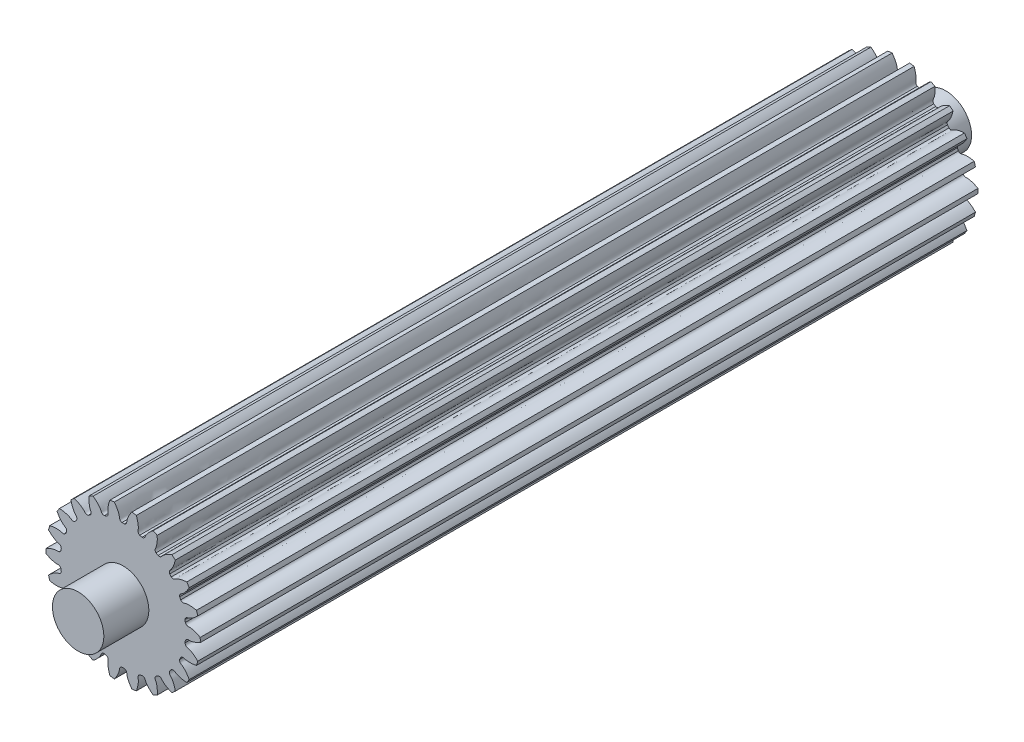
SolidWorks part; units mm, degrees
ref_plane "前视基准面" through (0, 0, 0) normal (0, 0, 1) x (1, 0, 0)
ref_plane "上视基准面" through (0, 0, 0) normal (0, 1, 0) x (1, 0, 0)
ref_plane "右视基准面" through (0, 0, 0) normal (1, 0, 0) x (0, 0, -1)
sketch "草图1" plane through (0, 0, 0) normal (0, 0, 1) x (1, 0, 0)
  circle A0 centre (0, 0) radius 12
extrude "凸台-拉伸1" add sketch "草图1" along normal blind 30
ref_axis "基准轴1" through (0, 0, -1.5) along (0, 0, 1)
sketch "草图2" plane through (0, 0, 0) normal (0, 0, 1) x (1, 0, 0)
  line L0 (0, 0) -> (0, 12) construction
  circle A0 centre (0, 0) radius 12 construction
  arc A1 (0.1857, 9.7482) -> (-0.1857, 9.7482) centre (0, 0) ccw
  arc A2 (3.0856, 13.5599) -> (-3.0856, 13.5599) centre (0, 0) ccw
  spline S0 degree 3 poles (0.1857, 9.7482) (0.5882, 9.8762) (0.5483, 10.1518) (0.5996, 10.4216) (0.606, 10.4519) (0.6139, 10.4862) (0.6235, 10.5243) (0.6349, 10.5661) (0.6484, 10.6117) (0.664, 10.661) (0.6819, 10.7139) (0.7023, 10.7703) (0.7253, 10.8301) (0.7511, 10.8933) (0.7797, 10.9597) (0.8114, 11.0293) (0.8462, 11.1021) (0.8843, 11.1778) (0.9259, 11.2563) (0.9711, 11.3377) (1.0199, 11.4217) (1.0726, 11.5082) (1.1292, 11.5972) (1.1899, 11.6884) (1.2547, 11.7818) (1.3238, 11.8773) (1.3973, 11.9746) (1.4753, 12.0737) (1.5579, 12.1744) (1.6452, 12.2766) (1.7372, 12.3802) (1.8341, 12.4849) (1.9359, 12.5906) (2.0428, 12.6972) (2.1547, 12.8044) (2.2718, 12.9123) (2.3942, 13.0205) (2.5218, 13.1289) (2.6548, 13.2373) (2.8415, 13.3834) (2.9864, 13.49) (3.0856, 13.5599) knots 0 0 0 0 0.157021 0.162531 0.168888 0.176093 0.184146 0.193046 0.202794 0.213389 0.224833 0.237123 0.250262 0.264248 0.279082 0.294763 0.311292 0.328669 0.346893 0.365965 0.385884 0.406652 0.428266 0.450729 0.474039 0.498197 0.523202 0.549055 0.575756 0.603304 0.6317 0.660944 0.691035 0.721974 0.75376 0.786395 0.819876 0.854206 0.889383 0.925408 1 1 1 1
  spline S1 degree 3 poles (-0.1857, 9.7482) (-0.5882, 9.8762) (-0.5483, 10.1518) (-0.5996, 10.4216) (-0.606, 10.4519) (-0.6139, 10.4862) (-0.6235, 10.5243) (-0.6349, 10.5661) (-0.6484, 10.6117) (-0.664, 10.661) (-0.6819, 10.7139) (-0.7023, 10.7703) (-0.7253, 10.8301) (-0.7511, 10.8933) (-0.7797, 10.9597) (-0.8114, 11.0293) (-0.8462, 11.1021) (-0.8843, 11.1778) (-0.9259, 11.2563) (-0.9711, 11.3377) (-1.0199, 11.4217) (-1.0726, 11.5082) (-1.1292, 11.5972) (-1.1899, 11.6884) (-1.2547, 11.7818) (-1.3238, 11.8773) (-1.3973, 11.9746) (-1.4753, 12.0737) (-1.5579, 12.1744) (-1.6452, 12.2766) (-1.7372, 12.3802) (-1.8341, 12.4849) (-1.9359, 12.5906) (-2.0428, 12.6972) (-2.1547, 12.8044) (-2.2718, 12.9123) (-2.3942, 13.0205) (-2.5218, 13.1289) (-2.6548, 13.2373) (-2.8415, 13.3834) (-2.9864, 13.49) (-3.0856, 13.5599) knots 0 0 0 0 0.157021 0.162531 0.168888 0.176093 0.184146 0.193046 0.202794 0.213389 0.224833 0.237123 0.250262 0.264248 0.279082 0.294763 0.311292 0.328669 0.346893 0.365965 0.385884 0.406652 0.428266 0.450729 0.474039 0.498197 0.523202 0.549055 0.575756 0.603304 0.6317 0.660944 0.691035 0.721974 0.75376 0.786395 0.819876 0.854206 0.889383 0.925408 1 1 1 1
extrude "切除-拉伸1" cut sketch "草图2" along normal through all
pattern_circular "阵列(圆周)1" count 22 every 16.364 about axis through (0, 0, -1.5) along (0, 0, 1) of "切除-拉伸1"
sketch "草图3" plane through (0, 0, 0) normal (0, 0, 1) x (1, 0, 0)
  circle A0 centre (0, 0) radius 11 construction
  dimension "Dn" = 22
sketch "草图4" plane through (0, 0, 0) normal (0, 0, -1) x (-1, 0, 0)
  arc A45 (2.9245, 9.3011) -> (2.5682, 9.4057) centre (0, 0) ccw
  arc A46 (2.0557, 11.8226) -> (1.3584, 11.9229) centre (0, 0) ccw
  arc A47 (0.1857, 9.7482) -> (-0.1857, 9.7482) centre (0, 0) ccw
  arc A48 (-1.3584, 11.9229) -> (-2.0557, 11.8226) centre (0, 0) ccw
  arc A49 (-2.5682, 9.4057) -> (-2.9245, 9.3011) centre (0, 0) ccw
  arc A50 (-4.6624, 11.0572) -> (-5.3032, 10.7646) centre (0, 0) ccw
  arc A51 (-5.1141, 8.3011) -> (-5.4265, 8.1004) centre (0, 0) ccw
  arc A52 (-7.5887, 9.2958) -> (-8.1211, 8.8344) centre (0, 0) ccw
  arc A53 (-7.2456, 6.5241) -> (-7.4888, 6.2434) centre (0, 0) ccw
  arc A54 (-9.9003, 6.7812) -> (-10.2811, 6.1886) centre (0, 0) ccw
  arc A55 (-8.7902, 4.2184) -> (-8.9444, 3.8807) centre (0, 0) ccw
  arc A56 (-11.4097, 3.7173) -> (-11.6082, 3.0414) centre (0, 0) ccw
  arc A57 (-9.6226, 1.5711) -> (-9.6754, 1.2035) centre (0, 0) ccw
  arc A58 (-11.9948, 0.3522) -> (-11.9948, -0.3522) centre (0, 0) ccw
  arc A59 (-9.6754, -1.2035) -> (-9.6226, -1.5711) centre (0, 0) ccw
  arc A60 (-11.6082, -3.0414) -> (-11.4097, -3.7173) centre (0, 0) ccw
  arc A61 (-8.9444, -3.8807) -> (-8.7902, -4.2184) centre (0, 0) ccw
  arc A62 (-10.2811, -6.1886) -> (-9.9003, -6.7812) centre (0, 0) ccw
  arc A63 (-7.4888, -6.2434) -> (-7.2456, -6.5241) centre (0, 0) ccw
  arc A64 (-8.1211, -8.8344) -> (-7.5887, -9.2958) centre (0, 0) ccw
  arc A65 (-5.4265, -8.1004) -> (-5.1141, -8.3011) centre (0, 0) ccw
  arc A66 (-5.3032, -10.7646) -> (-4.6624, -11.0572) centre (0, 0) ccw
  arc A67 (-2.9245, -9.3011) -> (-2.5682, -9.4057) centre (0, 0) ccw
  arc A68 (-2.0557, -11.8226) -> (-1.3584, -11.9229) centre (0, 0) ccw
  arc A69 (-0.1857, -9.7482) -> (0.1857, -9.7482) centre (0, 0) ccw
  arc A70 (1.3584, -11.9229) -> (2.0557, -11.8226) centre (0, 0) ccw
  arc A71 (2.5682, -9.4057) -> (2.9245, -9.3011) centre (0, 0) ccw
  arc A72 (4.6624, -11.0572) -> (5.3032, -10.7646) centre (0, 0) ccw
  arc A73 (5.1141, -8.3011) -> (5.4265, -8.1004) centre (0, 0) ccw
  arc A74 (7.5887, -9.2958) -> (8.1211, -8.8344) centre (0, 0) ccw
  arc A75 (7.2456, -6.5241) -> (7.4888, -6.2434) centre (0, 0) ccw
  arc A76 (9.9003, -6.7812) -> (10.2811, -6.1886) centre (0, 0) ccw
  arc A77 (8.7902, -4.2184) -> (8.9444, -3.8807) centre (0, 0) ccw
  arc A78 (11.4097, -3.7173) -> (11.6082, -3.0414) centre (0, 0) ccw
  arc A79 (9.6226, -1.5711) -> (9.6754, -1.2035) centre (0, 0) ccw
  arc A80 (11.9948, -0.3522) -> (11.9948, 0.3522) centre (0, 0) ccw
  arc A81 (9.6754, 1.2035) -> (9.6226, 1.5711) centre (0, 0) ccw
  arc A82 (11.6082, 3.0414) -> (11.4097, 3.7173) centre (0, 0) ccw
  arc A83 (8.9444, 3.8807) -> (8.7902, 4.2184) centre (0, 0) ccw
  arc A84 (10.2811, 6.1886) -> (9.9003, 6.7812) centre (0, 0) ccw
  arc A85 (7.4888, 6.2434) -> (7.2456, 6.5241) centre (0, 0) ccw
  arc A86 (8.1211, 8.8344) -> (7.5887, 9.2958) centre (0, 0) ccw
  arc A87 (5.4265, 8.1004) -> (5.1141, 8.3011) centre (0, 0) ccw
  arc A88 (5.3032, 10.7646) -> (4.6624, 11.0572) centre (0, 0) ccw
  arc A89 (2.9245, 9.3011) -> (2.5682, 9.4057) centre (0, 0) ccw
  arc A90 (2.0557, 11.8226) -> (1.3584, 11.9229) centre (0, 0) ccw
  arc A91 (0.1857, 9.7482) -> (-0.1857, 9.7482) centre (0, 0) ccw
  arc A92 (-1.3584, 11.9229) -> (-2.0557, 11.8226) centre (0, 0) ccw
  arc A93 (-2.5682, 9.4057) -> (-2.9245, 9.3011) centre (0, 0) ccw
  arc A94 (-4.6624, 11.0572) -> (-5.3032, 10.7646) centre (0, 0) ccw
  arc A95 (-5.1141, 8.3011) -> (-5.4265, 8.1004) centre (0, 0) ccw
  arc A96 (-7.5887, 9.2958) -> (-8.1211, 8.8344) centre (0, 0) ccw
  arc A97 (-7.2456, 6.5241) -> (-7.4888, 6.2434) centre (0, 0) ccw
  arc A98 (-9.9003, 6.7812) -> (-10.2811, 6.1886) centre (0, 0) ccw
  arc A99 (-8.7902, 4.2184) -> (-8.9444, 3.8807) centre (0, 0) ccw
  arc A100 (-11.4097, 3.7173) -> (-11.6082, 3.0414) centre (0, 0) ccw
  arc A101 (-9.6226, 1.5711) -> (-9.6754, 1.2035) centre (0, 0) ccw
  arc A102 (-11.9948, 0.3522) -> (-11.9948, -0.3522) centre (0, 0) ccw
  arc A103 (-9.6754, -1.2035) -> (-9.6226, -1.5711) centre (0, 0) ccw
  arc A104 (-11.6082, -3.0414) -> (-11.4097, -3.7173) centre (0, 0) ccw
  arc A105 (-8.9444, -3.8807) -> (-8.7902, -4.2184) centre (0, 0) ccw
  arc A106 (-10.2811, -6.1886) -> (-9.9003, -6.7812) centre (0, 0) ccw
  arc A107 (-7.4888, -6.2434) -> (-7.2456, -6.5241) centre (0, 0) ccw
  arc A108 (-8.1211, -8.8344) -> (-7.5887, -9.2958) centre (0, 0) ccw
  arc A109 (-5.4265, -8.1004) -> (-5.1141, -8.3011) centre (0, 0) ccw
  arc A110 (-5.3032, -10.7646) -> (-4.6624, -11.0572) centre (0, 0) ccw
  arc A111 (-2.9245, -9.3011) -> (-2.5682, -9.4057) centre (0, 0) ccw
  arc A112 (-2.0557, -11.8226) -> (-1.3584, -11.9229) centre (0, 0) ccw
  arc A113 (-0.1857, -9.7482) -> (0.1857, -9.7482) centre (0, 0) ccw
  arc A114 (1.3584, -11.9229) -> (2.0557, -11.8226) centre (0, 0) ccw
  arc A115 (2.5682, -9.4057) -> (2.9245, -9.3011) centre (0, 0) ccw
  arc A116 (4.6624, -11.0572) -> (5.3032, -10.7646) centre (0, 0) ccw
  arc A117 (5.1141, -8.3011) -> (5.4265, -8.1004) centre (0, 0) ccw
  arc A118 (7.5887, -9.2958) -> (8.1211, -8.8344) centre (0, 0) ccw
  arc A119 (7.2456, -6.5241) -> (7.4888, -6.2434) centre (0, 0) ccw
  arc A120 (9.9003, -6.7812) -> (10.2811, -6.1886) centre (0, 0) ccw
  arc A121 (8.7902, -4.2184) -> (8.9444, -3.8807) centre (0, 0) ccw
  arc A122 (11.4097, -3.7173) -> (11.6082, -3.0414) centre (0, 0) ccw
  arc A123 (9.6226, -1.5711) -> (9.6754, -1.2035) centre (0, 0) ccw
  arc A124 (11.9948, -0.3522) -> (11.9948, 0.3522) centre (0, 0) ccw
  arc A125 (9.6754, 1.2035) -> (9.6226, 1.5711) centre (0, 0) ccw
  arc A126 (11.6082, 3.0414) -> (11.4097, 3.7173) centre (0, 0) ccw
  arc A127 (8.9444, 3.8807) -> (8.7902, 4.2184) centre (0, 0) ccw
  arc A128 (10.2811, 6.1886) -> (9.9003, 6.7812) centre (0, 0) ccw
  arc A129 (7.4888, 6.2434) -> (7.2456, 6.5241) centre (0, 0) ccw
  arc A130 (8.1211, 8.8344) -> (7.5887, 9.2958) centre (0, 0) ccw
  arc A131 (5.4265, 8.1004) -> (5.1141, 8.3011) centre (0, 0) ccw
  arc A132 (5.3032, 10.7646) -> (4.6624, 11.0572) centre (0, 0) ccw
  spline S44 degree 3 poles (-7496.4592, 2789.5016) (226.4744, -158.9957) (28.5821, 31.5473) (4.2738, 10.7434) (4.1283, 10.6084) (3.9999, 10.4794) (3.888, 10.3576) (3.7917, 10.2441) (3.7102, 10.1398) (3.6518, 10.0587) (3.6037, 9.9872) (3.5713, 9.9359) (3.5381, 9.8795) (3.5167, 9.8409) (0.6369, 4.2172) (43.7494, -24.3223) (-6732.0995, 4323.7051) knots -19.040021 -19.040021 -19.040021 -19.040021 0.549271 0.593348 0.634035 0.671331 0.705237 0.735752 0.762877 0.786611 0.797206 0.815854 0.823907 0.837469 0.842979 4.709556 4.709556 4.709556 4.709556 only from (4.6624, 11.0572) to (2.9245, 9.3011)
  spline S45 degree 3 poles (7999.956, -2.3149) (-49.9496, 3.1915) (1.7443, 3.8923) (2.3619, 10.18) (2.3658, 10.2385) (2.3681, 10.3211) (2.3668, 10.4204) (2.3608, 10.536) (2.3486, 10.6678) (2.329, 10.8154) (2.3007, 10.9784) (2.2624, 11.1562) (2.213, 11.3485) (2.1511, 11.5544) (-8.9188, 43.6975) (-289.9121, -23.2582) (7822.5066, -1669.0431) knots -3.709393 -3.709393 -3.709393 -3.709393 0.157021 0.162531 0.176093 0.193046 0.213389 0.237123 0.264248 0.294763 0.328669 0.365965 0.406652 0.450729 0.498197 21.310868 21.310868 21.310868 21.310868 only from (2.5682, 9.4057) to (2.0557, 11.8226)
  spline S46 degree 3 poles (-7978.6933, 564.5106) (262.0949, -88.75) (18.5364, 38.3219) (1.0739, 11.5123) (0.9723, 11.3417) (0.8855, 11.1818) (0.8124, 11.0334) (0.752, 10.8973) (0.7032, 10.7743) (0.6701, 10.6801) (0.644, 10.5979) (0.6274, 10.5396) (0.6113, 10.4761) (0.6018, 10.4331) (-0.577, 4.2258) (48.8297, -11.0115) (-7677.5306, 2251.913) knots -19.040021 -19.040021 -19.040021 -19.040021 0.549271 0.593348 0.634035 0.671331 0.705237 0.735752 0.762877 0.786611 0.797206 0.815854 0.823907 0.837469 0.842979 4.709556 4.709556 4.709556 4.709556 only from (1.3584, 11.9229) to (0.1857, 9.7482)
  spline S47 degree 3 poles (7676.5537, 2251.6269) (-48.8255, -11.0102) (0.577, 4.2261) (-0.6018, 10.4331) (-0.6145, 10.4903) (-0.6356, 10.5702) (-0.6648, 10.6651) (-0.7032, 10.7743) (-0.752, 10.8973) (-0.8124, 11.0334) (-0.8855, 11.1818) (-0.9723, 11.3417) (-1.0739, 11.5123) (-1.1913, 11.6924) (-20.8685, 39.4148) (-271.616, -103.9938) (7975.8639, 602.4197) knots -3.709393 -3.709393 -3.709393 -3.709393 0.157021 0.162531 0.176093 0.193046 0.213389 0.237123 0.264248 0.294763 0.328669 0.365965 0.406652 0.450729 0.498197 21.310868 21.310868 21.310868 21.310868 only from (-0.1857, 9.7482) to (-1.3584, 11.9229)
  spline S48 degree 3 poles (-7814.5412, -1706.2138) (276.482, -11.3143) (6.989, 41.9919) (-2.213, 11.3485) (-2.2624, 11.1562) (-2.3007, 10.9784) (-2.329, 10.8154) (-2.3486, 10.6678) (-2.3608, 10.536) (-2.366, 10.4362) (-2.3678, 10.3501) (-2.3674, 10.2894) (-2.3649, 10.224) (-2.3619, 10.18) (-1.7442, 3.8921) (49.954, 3.1915) (-8000.9739, -2.3156) knots -19.040021 -19.040021 -19.040021 -19.040021 0.549271 0.593348 0.634035 0.671331 0.705237 0.735752 0.762877 0.786611 0.797206 0.815854 0.823907 0.837469 0.842979 4.709556 4.709556 4.709556 4.709556 only from (-2.0557, 11.8226) to (-2.5682, 9.4057)
  spline S49 degree 3 poles (6731.2428, 4323.1553) (-43.7458, -24.3199) (-0.637, 4.2175) (-3.5167, 9.8409) (-3.5451, 9.8922) (-3.5879, 9.963) (-3.6426, 10.0458) (-3.7102, 10.1398) (-3.7917, 10.2441) (-3.888, 10.3576) (-3.9999, 10.4794) (-4.1283, 10.6084) (-4.2738, 10.7434) (-4.4372, 10.8832) (-31.1276, 31.9389) (-231.3152, -176.3044) (7483.0641, 2825.078) knots -3.709393 -3.709393 -3.709393 -3.709393 0.157021 0.162531 0.176093 0.193046 0.213389 0.237123 0.264248 0.294763 0.328669 0.365965 0.406652 0.450729 0.498197 21.310868 21.310868 21.310868 21.310868 only from (-2.9245, 9.3011) to (-4.6624, 11.0572)
  spline S50 degree 3 poles (-7017.3014, -3838.7108) (268.4701, 67.0379) (-5.1246, 42.26) (-5.3206, 10.2653) (-5.3138, 10.0669) (-5.3004, 9.8855) (-5.2817, 9.7211) (-5.2589, 9.574) (-5.2335, 9.4441) (-5.2104, 9.3469) (-5.1879, 9.2637) (-5.1704, 9.2057) (-5.1495, 9.1436) (-5.1343, 9.1022) (-2.7701, 3.243) (47.0314, 17.1359) (-7676.2259, -2256.3566) knots -19.040021 -19.040021 -19.040021 -19.040021 0.549271 0.593348 0.634035 0.671331 0.705237 0.735752 0.762877 0.786611 0.797206 0.815854 0.823907 0.837469 0.842979 4.709556 4.709556 4.709556 4.709556 only from (-5.3032, 10.7646) to (-5.1141, 8.3011)
  spline S51 degree 3 poles (5240.6065, 6044.4474) (-35.1221, -35.6594) (-1.7994, 3.8672) (-6.1468, 8.4515) (-6.1884, 8.4928) (-6.2494, 8.5486) (-6.3253, 8.6126) (-6.4166, 8.6838) (-6.5242, 8.7609) (-6.6486, 8.8427) (-6.7903, 8.928) (-6.9498, 9.0156) (-7.1274, 9.1041) (-7.3236, 9.1923) (-38.865, 21.8754) (-172.2747, -234.3319) (6384.031, 4818.8653) knots -3.709393 -3.709393 -3.709393 -3.709393 0.157021 0.162531 0.176093 0.193046 0.213389 0.237123 0.264248 0.294763 0.328669 0.365965 0.406652 0.450729 0.498197 21.310868 21.310868 21.310868 21.310868 only from (-5.4265, 8.1004) to (-7.5887, 9.2958)
  spline S52 degree 3 poles (-5651.5616, -5660.2183) (238.7084, 139.9592) (-16.823, 39.1044) (-7.9971, 8.3505) (-7.9348, 8.1621) (-7.8708, 7.9917) (-7.8065, 7.8393) (-7.7432, 7.7046) (-7.6822, 7.5871) (-7.6327, 7.5003) (-7.5876, 7.4269) (-7.5545, 7.3761) (-7.517, 7.3224) (-7.4907, 7.287) (-3.5716, 2.3312) (40.2985, 29.692) (-6729.5957, -4327.6011) knots -19.040021 -19.040021 -19.040021 -19.040021 0.549271 0.593348 0.634035 0.671331 0.705237 0.735752 0.762877 0.786611 0.797206 0.815854 0.823907 0.837469 0.842979 4.709556 4.709556 4.709556 4.709556 only from (-8.1211, 8.8344) to (-7.2456, 6.5241)
  spline S53 degree 3 poles (3325.4075, 7276.0543) (-23.653, -44.11) (-2.816, 3.2036) (-8.2789, 6.3774) (-8.3304, 6.4053) (-8.4047, 6.4416) (-8.4955, 6.4817) (-8.6032, 6.5243) (-8.7281, 6.5679) (-8.8705, 6.6114) (-9.0305, 6.6533) (-9.2082, 6.6924) (-9.4036, 6.7273) (-9.6167, 6.7566) (-43.4537, 10.0398) (-99.2774, -273.3752) (4767.8017, 6422.2568) knots -3.709393 -3.709393 -3.709393 -3.709393 0.157021 0.162531 0.176093 0.193046 0.213389 0.237123 0.264248 0.294763 0.328669 0.365965 0.406652 0.450729 0.498197 21.310868 21.310868 21.310868 21.310868 only from (-7.4888, 6.2434) to (-9.9003, 6.7812)
  spline S54 degree 3 poles (-3827.9659, -7023.1686) (189.608, 201.5418) (-27.1586, 32.7808) (-10.0258, 5.7592) (-9.9129, 5.596) (-9.8035, 5.4506) (-9.6989, 5.3224) (-9.6002, 5.211) (-9.5086, 5.1155) (-9.4366, 5.0462) (-9.3727, 4.9884) (-9.3266, 4.949) (-9.2755, 4.908) (-9.2403, 4.8814) (-4.0837, 1.2306) (30.3009, 39.8427) (-5237.7736, -6048.249) knots -19.040021 -19.040021 -19.040021 -19.040021 0.549271 0.593348 0.634035 0.671331 0.705237 0.735752 0.762877 0.786611 0.797206 0.815854 0.823907 0.837469 0.842979 4.709556 4.709556 4.709556 4.709556 only from (-10.2811, 6.1886) to (-8.7902, 4.2184)
  spline S55 degree 3 poles (1140.8038, 7918.1985) (-10.2676, -48.987) (-3.6045, 2.2804) (-9.7402, 3.7867) (-9.7976, 3.7989) (-9.8791, 3.8128) (-9.9775, 3.8257) (-10.0928, 3.8362) (-10.225, 3.8429) (-10.3738, 3.8445) (-10.5392, 3.8396) (-10.7207, 3.8271) (-10.918, 3.8055) (-11.1307, 3.7736) (-44.522, -2.6092) (-18.2373, -290.2712) (2765.3134, 7505.3552) knots -3.709393 -3.709393 -3.709393 -3.709393 0.157021 0.162531 0.176093 0.193046 0.213389 0.237123 0.264248 0.294763 0.328669 0.365965 0.406652 0.450729 0.498197 21.310868 21.310868 21.310868 21.310868 only from (-8.9444, 3.8807) to (-11.4097, 3.7173)
  spline S56 degree 3 poles (-1694.2511, -7817.1435) (125.1466, 246.7967) (-35.2939, 23.8015) (-11.2422, 2.7013) (-11.0879, 2.5765) (-10.942, 2.4678) (-10.8055, 2.3743) (-10.6794, 2.2952) (-10.5646, 2.2294) (-10.476, 2.1832) (-10.3984, 2.1457) (-10.3431, 2.1209) (-10.2825, 2.096) (-10.2412, 2.0804) (-4.2649, 0.0302) (17.8486, 46.7655) (-3321.6183, -7278.9038) knots -19.040021 -19.040021 -19.040021 -19.040021 0.549271 0.593348 0.634035 0.671331 0.705237 0.735752 0.762877 0.786611 0.797206 0.815854 0.823907 0.837469 0.842979 4.709556 4.709556 4.709556 4.709556 only from (-11.6082, 3.0414) to (-9.6226, 1.5711)
  spline S57 degree 3 poles (-1136.2211, 7918.8574) (3.9495, -49.8954) (-4.101, 1.1726) (-10.4125, 0.8891) (-10.4709, 0.8847) (-10.5531, 0.8751) (-10.6512, 0.8598) (-10.7647, 0.8373) (-10.8934, 0.8065) (-11.0367, 0.7661) (-11.194, 0.7149) (-11.3647, 0.6517) (-11.5479, 0.5754) (-11.743, 0.4849) (-41.9835, -15.0468) (64.2803, -283.6512) (538.7958, 7980.4144) knots -3.709393 -3.709393 -3.709393 -3.709393 0.157021 0.162531 0.176093 0.193046 0.213389 0.237123 0.264248 0.294763 0.328669 0.365965 0.406652 0.450729 0.498197 21.310868 21.310868 21.310868 21.310868 only from (-9.6754, 1.2035) to (-11.9948, 0.3522)
  spline S58 degree 3 poles (576.7218, -7977.82) (50.5467, 272.0576) (-40.5699, 12.894) (-11.5479, -0.5754) (-11.3647, -0.6517) (-11.194, -0.7149) (-11.0367, -0.7661) (-10.8934, -0.8065) (-10.7647, -0.8373) (-10.6667, -0.8567) (-10.5817, -0.8708) (-10.5216, -0.879) (-10.4565, -0.8858) (-10.4125, -0.8891) (-4.1007, -1.1726) (3.9502, 49.8997) (-1136.3653, -7919.8651) knots -19.040021 -19.040021 -19.040021 -19.040021 0.549271 0.593348 0.634035 0.671331 0.705237 0.735752 0.762877 0.786611 0.797206 0.815854 0.823907 0.837469 0.842979 4.709556 4.709556 4.709556 4.709556 only from (-11.9948, -0.3522) to (-9.6754, -1.2035)
  spline S59 degree 3 poles (-3321.1961, 7277.9776) (17.8467, -46.7616) (-4.2652, -0.0303) (-10.2412, -2.0804) (-10.296, -2.1012) (-10.3722, -2.1335) (-10.4619, -2.1758) (-10.5646, -2.2294) (-10.6794, -2.2952) (-10.8055, -2.3743) (-10.942, -2.4678) (-11.0879, -2.5765) (-11.2422, -2.7014) (-11.4039, -2.8432) (-36.0437, -26.2654) (141.5903, -254.0515) (-1731.3717, 7808.9478) knots -3.709393 -3.709393 -3.709393 -3.709393 0.157021 0.162531 0.176093 0.193046 0.213389 0.237123 0.264248 0.294763 0.328669 0.365965 0.406652 0.450729 0.498197 21.310868 21.310868 21.310868 21.310868 only from (-9.6226, -1.5711) to (-11.6082, -3.0414)
  spline S60 degree 3 poles (2800.9721, -7492.1809) (-28.1483, 275.278) (-42.5592, 0.9418) (-10.918, -3.8055) (-10.7207, -3.8271) (-10.5392, -3.8396) (-10.3738, -3.8445) (-10.225, -3.8429) (-10.0928, -3.8362) (-9.9933, -3.8272) (-9.9078, -3.8167) (-9.8478, -3.8076) (-9.7834, -3.7958) (-9.7402, -3.7867) (-3.6042, -2.2804) (-10.2682, 48.9913) (1140.9493, -7919.206) knots -19.040021 -19.040021 -19.040021 -19.040021 0.549271 0.593348 0.634035 0.671331 0.705237 0.735752 0.762877 0.786611 0.797206 0.815854 0.823907 0.837469 0.842979 4.709556 4.709556 4.709556 4.709556 only from (-11.4097, -3.7173) to (-8.9444, -3.8807)
  spline S61 degree 3 poles (-5237.1076, 6047.4793) (30.2981, -39.8394) (-4.0839, -1.2307) (-9.2403, -4.8814) (-9.287, -4.9168) (-9.351, -4.9692) (-9.4251, -5.0352) (-9.5086, -5.1155) (-9.6002, -5.211) (-9.6989, -5.3224) (-9.8035, -5.4506) (-9.9129, -5.596) (-10.0258, -5.7592) (-10.1409, -5.9408) (-27.1838, -35.3562) (207.4295, -203.8701) (-3861.2738, 7004.8468) knots -3.709393 -3.709393 -3.709393 -3.709393 0.157021 0.162531 0.176093 0.193046 0.213389 0.237123 0.264248 0.294763 0.328669 0.365965 0.406652 0.450729 0.498197 21.310868 21.310868 21.310868 21.310868 only from (-8.7902, -4.2184) to (-10.2811, -6.1886)
  spline S62 degree 3 poles (4798.3044, -6399.5699) (-104.5629, 256.197) (-41.1006, -11.0867) (-9.4036, -6.7273) (-9.2082, -6.6924) (-9.0305, -6.6533) (-8.8705, -6.6114) (-8.7281, -6.5679) (-8.6032, -6.5243) (-8.5102, -6.4876) (-8.4311, -6.4535) (-8.3761, -6.4279) (-8.3177, -6.3984) (-8.2789, -6.3774) (-2.8158, -3.2034) (-23.6547, 44.114) (3325.831, -7276.9799) knots -19.040021 -19.040021 -19.040021 -19.040021 0.549271 0.593348 0.634035 0.671331 0.705237 0.735752 0.762877 0.786611 0.797206 0.815854 0.823907 0.837469 0.842979 4.709556 4.709556 4.709556 4.709556 only from (-9.9003, -6.7812) to (-7.4888, -6.2434)
  spline S63 degree 3 poles (-6728.7397, 4327.0502) (40.2948, -29.6897) (-3.5717, -2.3314) (-7.4907, -7.287) (-7.5256, -7.3341) (-7.5722, -7.4024) (-7.6248, -7.4866) (-7.6822, -7.5871) (-7.7432, -7.7046) (-7.8065, -7.8393) (-7.8708, -7.9917) (-7.9348, -8.1621) (-7.9971, -8.3505) (-8.0564, -8.5572) (-16.1217, -41.5826) (256.4639, -137.1723) (-5678.3585, 5633.2547) knots -3.709393 -3.709393 -3.709393 -3.709393 0.157021 0.162531 0.176093 0.193046 0.213389 0.237123 0.264248 0.294763 0.328669 0.365965 0.406652 0.450729 0.498197 21.310868 21.310868 21.310868 21.310868 only from (-7.2456, -6.5241) to (-8.1211, -8.8344)
  spline S64 degree 3 poles (6406.9065, -4788.5038) (-172.5064, 216.3604) (-36.3122, -22.2169) (-7.1274, -9.1041) (-6.9498, -9.0156) (-6.7903, -8.928) (-6.6486, -8.8427) (-6.5242, -8.7609) (-6.4166, -8.6838) (-6.3378, -8.6224) (-6.2715, -8.5674) (-6.2259, -8.5273) (-6.1781, -8.4826) (-6.1468, -8.4515) (-1.7992, -3.867) (-35.1249, 35.6627) (5241.2736, -6045.2162) knots -19.040021 -19.040021 -19.040021 -19.040021 0.549271 0.593348 0.634035 0.671331 0.705237 0.735752 0.762877 0.786611 0.797206 0.815854 0.823907 0.837469 0.842979 4.709556 4.709556 4.709556 4.709556 only from (-7.5887, -9.2958) to (-5.4265, -8.1004)
  spline S65 degree 3 poles (-7675.2494, 2256.0692) (47.0272, -17.1347) (-2.7702, -3.2433) (-5.1343, -9.1022) (-5.1545, -9.1572) (-5.18, -9.2359) (-5.2067, -9.3315) (-5.2335, -9.4441) (-5.2589, -9.574) (-5.2817, -9.7211) (-5.3004, -9.8855) (-5.3138, -10.0669) (-5.3206, -10.2653) (-5.3192, -10.4804) (-3.7535, -44.4402) (284.7212, -59.3616) (-7035.4164, 3805.2899) knots -3.709393 -3.709393 -3.709393 -3.709393 0.157021 0.162531 0.176093 0.193046 0.213389 0.237123 0.264248 0.294763 0.328669 0.365965 0.406652 0.450729 0.498197 21.310868 21.310868 21.310868 21.310868 only from (-5.1141, -8.3011) to (-5.3032, -10.7646)
  spline S66 degree 3 poles (7496.4592, -2789.5016) (-226.4744, 158.9957) (-28.5821, -31.5473) (-4.2738, -10.7434) (-4.1283, -10.6084) (-3.9999, -10.4794) (-3.888, -10.3576) (-3.7917, -10.2441) (-3.7102, -10.1398) (-3.6518, -10.0587) (-3.6037, -9.9872) (-3.5713, -9.9359) (-3.5381, -9.8795) (-3.5167, -9.8409) (-0.6369, -4.2172) (-43.7494, 24.3223) (6732.0995, -4323.7051) knots -19.040021 -19.040021 -19.040021 -19.040021 0.549271 0.593348 0.634035 0.671331 0.705237 0.735752 0.762877 0.786611 0.797206 0.815854 0.823907 0.837469 0.842979 4.709556 4.709556 4.709556 4.709556 only from (-4.6624, -11.0572) to (-2.9245, -9.3011)
  spline S67 degree 3 poles (-7999.956, 2.3149) (49.9496, -3.1915) (-1.7443, -3.8923) (-2.3619, -10.18) (-2.3658, -10.2385) (-2.3681, -10.3211) (-2.3668, -10.4204) (-2.3608, -10.536) (-2.3486, -10.6678) (-2.329, -10.8154) (-2.3007, -10.9784) (-2.2624, -11.1562) (-2.213, -11.3485) (-2.1511, -11.5544) (8.9188, -43.6975) (289.9121, 23.2582) (-7822.5066, 1669.0431) knots -3.709393 -3.709393 -3.709393 -3.709393 0.157021 0.162531 0.176093 0.193046 0.213389 0.237123 0.264248 0.294763 0.328669 0.365965 0.406652 0.450729 0.498197 21.310868 21.310868 21.310868 21.310868 only from (-2.5682, -9.4057) to (-2.0557, -11.8226)
  spline S68 degree 3 poles (7978.6933, -564.5106) (-262.0949, 88.75) (-18.5364, -38.3219) (-1.0739, -11.5123) (-0.9723, -11.3417) (-0.8855, -11.1818) (-0.8124, -11.0334) (-0.752, -10.8973) (-0.7032, -10.7743) (-0.6701, -10.6801) (-0.644, -10.5979) (-0.6274, -10.5396) (-0.6113, -10.4761) (-0.6018, -10.4331) (0.577, -4.2258) (-48.8297, 11.0115) (7677.5306, -2251.913) knots -19.040021 -19.040021 -19.040021 -19.040021 0.549271 0.593348 0.634035 0.671331 0.705237 0.735752 0.762877 0.786611 0.797206 0.815854 0.823907 0.837469 0.842979 4.709556 4.709556 4.709556 4.709556 only from (-1.3584, -11.9229) to (-0.1857, -9.7482)
  spline S69 degree 3 poles (-7676.5537, -2251.6269) (48.8255, 11.0102) (-0.577, -4.2261) (0.6018, -10.4331) (0.6145, -10.4903) (0.6356, -10.5702) (0.6648, -10.6651) (0.7032, -10.7743) (0.752, -10.8973) (0.8124, -11.0334) (0.8855, -11.1818) (0.9723, -11.3417) (1.0739, -11.5123) (1.1913, -11.6924) (20.8685, -39.4148) (271.616, 103.9938) (-7975.8639, -602.4197) knots -3.709393 -3.709393 -3.709393 -3.709393 0.157021 0.162531 0.176093 0.193046 0.213389 0.237123 0.264248 0.294763 0.328669 0.365965 0.406652 0.450729 0.498197 21.310868 21.310868 21.310868 21.310868 only from (0.1857, -9.7482) to (1.3584, -11.9229)
  spline S70 degree 3 poles (7814.5412, 1706.2138) (-276.482, 11.3143) (-6.989, -41.9919) (2.213, -11.3485) (2.2624, -11.1562) (2.3007, -10.9784) (2.329, -10.8154) (2.3486, -10.6678) (2.3608, -10.536) (2.366, -10.4362) (2.3678, -10.3501) (2.3674, -10.2894) (2.3649, -10.224) (2.3619, -10.18) (1.7442, -3.8921) (-49.954, -3.1915) (8000.9739, 2.3156) knots -19.040021 -19.040021 -19.040021 -19.040021 0.549271 0.593348 0.634035 0.671331 0.705237 0.735752 0.762877 0.786611 0.797206 0.815854 0.823907 0.837469 0.842979 4.709556 4.709556 4.709556 4.709556 only from (2.0557, -11.8226) to (2.5682, -9.4057)
  spline S71 degree 3 poles (-6731.2428, -4323.1553) (43.7458, 24.3199) (0.637, -4.2175) (3.5167, -9.8409) (3.5451, -9.8922) (3.5879, -9.963) (3.6426, -10.0458) (3.7102, -10.1398) (3.7917, -10.2441) (3.888, -10.3576) (3.9999, -10.4794) (4.1283, -10.6084) (4.2738, -10.7434) (4.4372, -10.8832) (31.1276, -31.9389) (231.3152, 176.3044) (-7483.0641, -2825.078) knots -3.709393 -3.709393 -3.709393 -3.709393 0.157021 0.162531 0.176093 0.193046 0.213389 0.237123 0.264248 0.294763 0.328669 0.365965 0.406652 0.450729 0.498197 21.310868 21.310868 21.310868 21.310868 only from (2.9245, -9.3011) to (4.6624, -11.0572)
  spline S72 degree 3 poles (7017.3014, 3838.7108) (-268.4701, -67.0379) (5.1246, -42.26) (5.3206, -10.2653) (5.3138, -10.0669) (5.3004, -9.8855) (5.2817, -9.7211) (5.2589, -9.574) (5.2335, -9.4441) (5.2104, -9.3469) (5.1879, -9.2637) (5.1704, -9.2057) (5.1495, -9.1436) (5.1343, -9.1022) (2.7701, -3.243) (-47.0314, -17.1359) (7676.2259, 2256.3566) knots -19.040021 -19.040021 -19.040021 -19.040021 0.549271 0.593348 0.634035 0.671331 0.705237 0.735752 0.762877 0.786611 0.797206 0.815854 0.823907 0.837469 0.842979 4.709556 4.709556 4.709556 4.709556 only from (5.3032, -10.7646) to (5.1141, -8.3011)
  spline S73 degree 3 poles (-5240.6065, -6044.4474) (35.1221, 35.6594) (1.7994, -3.8672) (6.1468, -8.4515) (6.1884, -8.4928) (6.2494, -8.5486) (6.3253, -8.6126) (6.4166, -8.6838) (6.5242, -8.7609) (6.6486, -8.8427) (6.7903, -8.928) (6.9498, -9.0156) (7.1274, -9.1041) (7.3236, -9.1923) (38.865, -21.8754) (172.2747, 234.3319) (-6384.031, -4818.8653) knots -3.709393 -3.709393 -3.709393 -3.709393 0.157021 0.162531 0.176093 0.193046 0.213389 0.237123 0.264248 0.294763 0.328669 0.365965 0.406652 0.450729 0.498197 21.310868 21.310868 21.310868 21.310868 only from (5.4265, -8.1004) to (7.5887, -9.2958)
  spline S74 degree 3 poles (5651.5616, 5660.2183) (-238.7084, -139.9592) (16.823, -39.1044) (7.9971, -8.3505) (7.9348, -8.1621) (7.8708, -7.9917) (7.8065, -7.8393) (7.7432, -7.7046) (7.6822, -7.5871) (7.6327, -7.5003) (7.5876, -7.4269) (7.5545, -7.3761) (7.517, -7.3224) (7.4907, -7.287) (3.5716, -2.3312) (-40.2985, -29.692) (6729.5957, 4327.6011) knots -19.040021 -19.040021 -19.040021 -19.040021 0.549271 0.593348 0.634035 0.671331 0.705237 0.735752 0.762877 0.786611 0.797206 0.815854 0.823907 0.837469 0.842979 4.709556 4.709556 4.709556 4.709556 only from (8.1211, -8.8344) to (7.2456, -6.5241)
  spline S75 degree 3 poles (-3325.4075, -7276.0543) (23.653, 44.11) (2.816, -3.2036) (8.2789, -6.3774) (8.3304, -6.4053) (8.4047, -6.4416) (8.4955, -6.4817) (8.6032, -6.5243) (8.7281, -6.5679) (8.8705, -6.6114) (9.0305, -6.6533) (9.2082, -6.6924) (9.4036, -6.7273) (9.6167, -6.7566) (43.4537, -10.0398) (99.2774, 273.3752) (-4767.8017, -6422.2568) knots -3.709393 -3.709393 -3.709393 -3.709393 0.157021 0.162531 0.176093 0.193046 0.213389 0.237123 0.264248 0.294763 0.328669 0.365965 0.406652 0.450729 0.498197 21.310868 21.310868 21.310868 21.310868 only from (7.4888, -6.2434) to (9.9003, -6.7812)
  spline S76 degree 3 poles (3827.9659, 7023.1686) (-189.608, -201.5418) (27.1586, -32.7808) (10.0258, -5.7592) (9.9129, -5.596) (9.8035, -5.4506) (9.6989, -5.3224) (9.6002, -5.211) (9.5086, -5.1155) (9.4366, -5.0462) (9.3727, -4.9884) (9.3266, -4.949) (9.2755, -4.908) (9.2403, -4.8814) (4.0837, -1.2306) (-30.3009, -39.8427) (5237.7736, 6048.249) knots -19.040021 -19.040021 -19.040021 -19.040021 0.549271 0.593348 0.634035 0.671331 0.705237 0.735752 0.762877 0.786611 0.797206 0.815854 0.823907 0.837469 0.842979 4.709556 4.709556 4.709556 4.709556 only from (10.2811, -6.1886) to (8.7902, -4.2184)
  spline S77 degree 3 poles (-1140.8038, -7918.1985) (10.2676, 48.987) (3.6045, -2.2804) (9.7402, -3.7867) (9.7976, -3.7989) (9.8791, -3.8128) (9.9775, -3.8257) (10.0928, -3.8362) (10.225, -3.8429) (10.3738, -3.8445) (10.5392, -3.8396) (10.7207, -3.8271) (10.918, -3.8055) (11.1307, -3.7736) (44.522, 2.6092) (18.2373, 290.2712) (-2765.3134, -7505.3552) knots -3.709393 -3.709393 -3.709393 -3.709393 0.157021 0.162531 0.176093 0.193046 0.213389 0.237123 0.264248 0.294763 0.328669 0.365965 0.406652 0.450729 0.498197 21.310868 21.310868 21.310868 21.310868 only from (8.9444, -3.8807) to (11.4097, -3.7173)
  spline S78 degree 3 poles (1694.2511, 7817.1435) (-125.1466, -246.7967) (35.2939, -23.8015) (11.2422, -2.7013) (11.0879, -2.5765) (10.942, -2.4678) (10.8055, -2.3743) (10.6794, -2.2952) (10.5646, -2.2294) (10.476, -2.1832) (10.3984, -2.1457) (10.3431, -2.1209) (10.2825, -2.096) (10.2412, -2.0804) (4.2649, -0.0302) (-17.8486, -46.7655) (3321.6183, 7278.9038) knots -19.040021 -19.040021 -19.040021 -19.040021 0.549271 0.593348 0.634035 0.671331 0.705237 0.735752 0.762877 0.786611 0.797206 0.815854 0.823907 0.837469 0.842979 4.709556 4.709556 4.709556 4.709556 only from (11.6082, -3.0414) to (9.6226, -1.5711)
  spline S79 degree 3 poles (1136.2211, -7918.8574) (-3.9495, 49.8954) (4.101, -1.1726) (10.4125, -0.8891) (10.4709, -0.8847) (10.5531, -0.8751) (10.6512, -0.8598) (10.7647, -0.8373) (10.8934, -0.8065) (11.0367, -0.7661) (11.194, -0.7149) (11.3647, -0.6517) (11.5479, -0.5754) (11.743, -0.4849) (41.9835, 15.0468) (-64.2803, 283.6512) (-538.7958, -7980.4144) knots -3.709393 -3.709393 -3.709393 -3.709393 0.157021 0.162531 0.176093 0.193046 0.213389 0.237123 0.264248 0.294763 0.328669 0.365965 0.406652 0.450729 0.498197 21.310868 21.310868 21.310868 21.310868 only from (9.6754, -1.2035) to (11.9948, -0.3522)
  spline S80 degree 3 poles (-576.7218, 7977.82) (-50.5467, -272.0576) (40.5699, -12.894) (11.5479, 0.5754) (11.3647, 0.6517) (11.194, 0.7149) (11.0367, 0.7661) (10.8934, 0.8065) (10.7647, 0.8373) (10.6667, 0.8567) (10.5817, 0.8708) (10.5216, 0.879) (10.4565, 0.8858) (10.4125, 0.8891) (4.1007, 1.1726) (-3.9502, -49.8997) (1136.3653, 7919.8651) knots -19.040021 -19.040021 -19.040021 -19.040021 0.549271 0.593348 0.634035 0.671331 0.705237 0.735752 0.762877 0.786611 0.797206 0.815854 0.823907 0.837469 0.842979 4.709556 4.709556 4.709556 4.709556 only from (11.9948, 0.3522) to (9.6754, 1.2035)
  spline S81 degree 3 poles (3321.1961, -7277.9776) (-17.8467, 46.7616) (4.2652, 0.0303) (10.2412, 2.0804) (10.296, 2.1012) (10.3722, 2.1335) (10.4619, 2.1758) (10.5646, 2.2294) (10.6794, 2.2952) (10.8055, 2.3743) (10.942, 2.4678) (11.0879, 2.5765) (11.2422, 2.7014) (11.4039, 2.8432) (36.0437, 26.2654) (-141.5903, 254.0515) (1731.3717, -7808.9478) knots -3.709393 -3.709393 -3.709393 -3.709393 0.157021 0.162531 0.176093 0.193046 0.213389 0.237123 0.264248 0.294763 0.328669 0.365965 0.406652 0.450729 0.498197 21.310868 21.310868 21.310868 21.310868 only from (9.6226, 1.5711) to (11.6082, 3.0414)
  spline S82 degree 3 poles (-2800.9721, 7492.1809) (28.1483, -275.278) (42.5592, -0.9418) (10.918, 3.8055) (10.7207, 3.8271) (10.5392, 3.8396) (10.3738, 3.8445) (10.225, 3.8429) (10.0928, 3.8362) (9.9933, 3.8272) (9.9078, 3.8167) (9.8478, 3.8076) (9.7834, 3.7958) (9.7402, 3.7867) (3.6042, 2.2804) (10.2682, -48.9913) (-1140.9493, 7919.206) knots -19.040021 -19.040021 -19.040021 -19.040021 0.549271 0.593348 0.634035 0.671331 0.705237 0.735752 0.762877 0.786611 0.797206 0.815854 0.823907 0.837469 0.842979 4.709556 4.709556 4.709556 4.709556 only from (11.4097, 3.7173) to (8.9444, 3.8807)
  spline S83 degree 3 poles (5237.1076, -6047.4793) (-30.2981, 39.8394) (4.0839, 1.2307) (9.2403, 4.8814) (9.287, 4.9168) (9.351, 4.9692) (9.4251, 5.0352) (9.5086, 5.1155) (9.6002, 5.211) (9.6989, 5.3224) (9.8035, 5.4506) (9.9129, 5.596) (10.0258, 5.7592) (10.1409, 5.9408) (27.1838, 35.3562) (-207.4295, 203.8701) (3861.2738, -7004.8468) knots -3.709393 -3.709393 -3.709393 -3.709393 0.157021 0.162531 0.176093 0.193046 0.213389 0.237123 0.264248 0.294763 0.328669 0.365965 0.406652 0.450729 0.498197 21.310868 21.310868 21.310868 21.310868 only from (8.7902, 4.2184) to (10.2811, 6.1886)
  spline S84 degree 3 poles (-4798.3044, 6399.5699) (104.5629, -256.197) (41.1006, 11.0867) (9.4036, 6.7273) (9.2082, 6.6924) (9.0305, 6.6533) (8.8705, 6.6114) (8.7281, 6.5679) (8.6032, 6.5243) (8.5102, 6.4876) (8.4311, 6.4535) (8.3761, 6.4279) (8.3177, 6.3984) (8.2789, 6.3774) (2.8158, 3.2034) (23.6547, -44.114) (-3325.831, 7276.9799) knots -19.040021 -19.040021 -19.040021 -19.040021 0.549271 0.593348 0.634035 0.671331 0.705237 0.735752 0.762877 0.786611 0.797206 0.815854 0.823907 0.837469 0.842979 4.709556 4.709556 4.709556 4.709556 only from (9.9003, 6.7812) to (7.4888, 6.2434)
  spline S85 degree 3 poles (6728.7397, -4327.0502) (-40.2948, 29.6897) (3.5717, 2.3314) (7.4907, 7.287) (7.5256, 7.3341) (7.5722, 7.4024) (7.6248, 7.4866) (7.6822, 7.5871) (7.7432, 7.7046) (7.8065, 7.8393) (7.8708, 7.9917) (7.9348, 8.1621) (7.9971, 8.3505) (8.0564, 8.5572) (16.1217, 41.5826) (-256.4639, 137.1723) (5678.3585, -5633.2547) knots -3.709393 -3.709393 -3.709393 -3.709393 0.157021 0.162531 0.176093 0.193046 0.213389 0.237123 0.264248 0.294763 0.328669 0.365965 0.406652 0.450729 0.498197 21.310868 21.310868 21.310868 21.310868 only from (7.2456, 6.5241) to (8.1211, 8.8344)
  spline S86 degree 3 poles (-6406.9065, 4788.5038) (172.5064, -216.3604) (36.3122, 22.2169) (7.1274, 9.1041) (6.9498, 9.0156) (6.7903, 8.928) (6.6486, 8.8427) (6.5242, 8.7609) (6.4166, 8.6838) (6.3378, 8.6224) (6.2715, 8.5674) (6.2259, 8.5273) (6.1781, 8.4826) (6.1468, 8.4515) (1.7992, 3.867) (35.1249, -35.6627) (-5241.2736, 6045.2162) knots -19.040021 -19.040021 -19.040021 -19.040021 0.549271 0.593348 0.634035 0.671331 0.705237 0.735752 0.762877 0.786611 0.797206 0.815854 0.823907 0.837469 0.842979 4.709556 4.709556 4.709556 4.709556 only from (7.5887, 9.2958) to (5.4265, 8.1004)
  spline S87 degree 3 poles (7675.2494, -2256.0692) (-47.0272, 17.1347) (2.7702, 3.2433) (5.1343, 9.1022) (5.1545, 9.1572) (5.18, 9.2359) (5.2067, 9.3315) (5.2335, 9.4441) (5.2589, 9.574) (5.2817, 9.7211) (5.3004, 9.8855) (5.3138, 10.0669) (5.3206, 10.2653) (5.3192, 10.4804) (3.7535, 44.4402) (-284.7212, 59.3616) (7035.4164, -3805.2899) knots -3.709393 -3.709393 -3.709393 -3.709393 0.157021 0.162531 0.176093 0.193046 0.213389 0.237123 0.264248 0.294763 0.328669 0.365965 0.406652 0.450729 0.498197 21.310868 21.310868 21.310868 21.310868 only from (5.1141, 8.3011) to (5.3032, 10.7646)
  spline S88 degree 3 poles (4.6624, 11.0572) (4.5848, 10.9995) (4.452, 10.8959) (4.2738, 10.7434) (4.1283, 10.6084) (3.9999, 10.4794) (3.888, 10.3576) (3.7917, 10.2441) (3.7102, 10.1398) (3.6518, 10.0587) (3.6037, 9.9872) (3.5713, 9.9359) (3.5381, 9.8795) (3.5167, 9.8409) (3.3862, 9.5861) (3.3468, 9.3104) (2.9245, 9.3011) knots 0.48979 0.48979 0.48979 0.48979 0.549271 0.593348 0.634035 0.671331 0.705237 0.735752 0.762877 0.786611 0.797206 0.815854 0.823907 0.837469 0.842979 1 1 1 1
  spline S89 degree 3 poles (2.5682, 9.4057) (2.2181, 9.6418) (2.334, 9.895) (2.3619, 10.18) (2.3658, 10.2385) (2.3681, 10.3211) (2.3668, 10.4204) (2.3608, 10.536) (2.3486, 10.6678) (2.329, 10.8154) (2.3007, 10.9784) (2.2624, 11.1562) (2.213, 11.3485) (2.1511, 11.5544) (2.0963, 11.7137) (2.0626, 11.8043) (2.0557, 11.8226) knots 0 0 0 0 0.157021 0.162531 0.176093 0.193046 0.213389 0.237123 0.264248 0.294763 0.328669 0.365965 0.406652 0.450729 0.498197 0.51021 0.51021 0.51021 0.51021
  spline S90 degree 3 poles (1.3584, 11.9229) (1.3002, 11.8457) (1.2019, 11.7088) (1.0739, 11.5123) (0.9723, 11.3417) (0.8855, 11.1818) (0.8124, 11.0334) (0.752, 10.8973) (0.7032, 10.7743) (0.6701, 10.6801) (0.644, 10.5979) (0.6274, 10.5396) (0.6113, 10.4761) (0.6018, 10.4331) (0.5483, 10.1518) (0.5882, 9.8762) (0.1857, 9.7482) knots 0.48979 0.48979 0.48979 0.48979 0.549271 0.593348 0.634035 0.671331 0.705237 0.735752 0.762877 0.786611 0.797206 0.815854 0.823907 0.837469 0.842979 1 1 1 1
  spline S91 degree 3 poles (-0.1857, 9.7482) (-0.5882, 9.8762) (-0.5483, 10.1518) (-0.6018, 10.4331) (-0.6145, 10.4903) (-0.6356, 10.5702) (-0.6648, 10.6651) (-0.7032, 10.7743) (-0.752, 10.8973) (-0.8124, 11.0334) (-0.8855, 11.1818) (-0.9723, 11.3417) (-1.0739, 11.5123) (-1.1913, 11.6924) (-1.2888, 11.8298) (-1.3466, 11.9073) (-1.3584, 11.9229) knots 0 0 0 0 0.157021 0.162531 0.176093 0.193046 0.213389 0.237123 0.264248 0.294763 0.328669 0.365965 0.406652 0.450729 0.498197 0.51021 0.51021 0.51021 0.51021
  spline S92 degree 3 poles (-2.0557, 11.8226) (-2.0898, 11.7321) (-2.1455, 11.5732) (-2.213, 11.3485) (-2.2624, 11.1562) (-2.3007, 10.9784) (-2.329, 10.8154) (-2.3486, 10.6678) (-2.3608, 10.536) (-2.366, 10.4362) (-2.3678, 10.3501) (-2.3674, 10.2894) (-2.3649, 10.224) (-2.3619, 10.18) (-2.334, 9.895) (-2.2181, 9.6418) (-2.5682, 9.4057) knots 0.48979 0.48979 0.48979 0.48979 0.549271 0.593348 0.634035 0.671331 0.705237 0.735752 0.762877 0.786611 0.797206 0.815854 0.823907 0.837469 0.842979 1 1 1 1
  spline S93 degree 3 poles (-2.9245, 9.3011) (-3.3468, 9.3104) (-3.3862, 9.5861) (-3.5167, 9.8409) (-3.5451, 9.8922) (-3.5879, 9.963) (-3.6426, 10.0458) (-3.7102, 10.1398) (-3.7917, 10.2441) (-3.888, 10.3576) (-3.9999, 10.4794) (-4.1283, 10.6084) (-4.2738, 10.7434) (-4.4372, 10.8832) (-4.5694, 10.9875) (-4.6468, 11.0456) (-4.6624, 11.0572) knots 0 0 0 0 0.157021 0.162531 0.176093 0.193046 0.213389 0.237123 0.264248 0.294763 0.328669 0.365965 0.406652 0.450729 0.498197 0.51021 0.51021 0.51021 0.51021
  spline S94 degree 3 poles (-5.3032, 10.7646) (-5.3105, 10.6681) (-5.3191, 10.4999) (-5.3206, 10.2653) (-5.3138, 10.0669) (-5.3004, 9.8855) (-5.2817, 9.7211) (-5.2589, 9.574) (-5.2335, 9.4441) (-5.2104, 9.3469) (-5.1879, 9.2637) (-5.1704, 9.2057) (-5.1495, 9.1436) (-5.1343, 9.1022) (-5.0272, 8.8367) (-4.8447, 8.6264) (-5.1141, 8.3011) knots 0.48979 0.48979 0.48979 0.48979 0.549271 0.593348 0.634035 0.671331 0.705237 0.735752 0.762877 0.786611 0.797206 0.815854 0.823907 0.837469 0.842979 1 1 1 1
  spline S95 degree 3 poles (-5.4265, 8.1004) (-5.8343, 7.9904) (-5.9498, 8.2438) (-6.1468, 8.4515) (-6.1884, 8.4928) (-6.2494, 8.5486) (-6.3253, 8.6126) (-6.4166, 8.6838) (-6.5242, 8.7609) (-6.6486, 8.8427) (-6.7903, 8.928) (-6.9498, 9.0156) (-7.1274, 9.1041) (-7.3236, 9.1923) (-7.4798, 9.2551) (-7.5704, 9.289) (-7.5887, 9.2958) knots 0 0 0 0 0.157021 0.162531 0.176093 0.193046 0.213389 0.237123 0.264248 0.294763 0.328669 0.365965 0.406652 0.450729 0.498197 0.51021 0.51021 0.51021 0.51021
  spline S96 degree 3 poles (-8.1211, 8.8344) (-8.1009, 8.7398) (-8.0618, 8.576) (-7.9971, 8.3505) (-7.9348, 8.1621) (-7.8708, 7.9917) (-7.8065, 7.8393) (-7.7432, 7.7046) (-7.6822, 7.5871) (-7.6327, 7.5003) (-7.5876, 7.4269) (-7.5545, 7.3761) (-7.517, 7.3224) (-7.4907, 7.287) (-7.3131, 7.0624) (-7.0788, 6.912) (-7.2456, 6.5241) knots 0.48979 0.48979 0.48979 0.48979 0.549271 0.593348 0.634035 0.671331 0.705237 0.735752 0.762877 0.786611 0.797206 0.815854 0.823907 0.837469 0.842979 1 1 1 1
  spline S97 degree 3 poles (-7.4888, 6.2434) (-7.8491, 6.023) (-8.0313, 6.2336) (-8.2789, 6.3774) (-8.3304, 6.4053) (-8.4047, 6.4416) (-8.4955, 6.4817) (-8.6032, 6.5243) (-8.7281, 6.5679) (-8.8705, 6.6114) (-9.0305, 6.6533) (-9.2082, 6.6924) (-9.4036, 6.7273) (-9.6167, 6.7566) (-9.7843, 6.7729) (-9.8808, 6.7799) (-9.9003, 6.7812) knots 0 0 0 0 0.157021 0.162531 0.176093 0.193046 0.213389 0.237123 0.264248 0.294763 0.328669 0.365965 0.406652 0.450729 0.498197 0.51021 0.51021 0.51021 0.51021
  spline S98 degree 3 poles (-10.2811, 6.1886) (-10.2351, 6.1035) (-10.1514, 5.9573) (-10.0258, 5.7592) (-9.9129, 5.596) (-9.8035, 5.4506) (-9.6989, 5.3224) (-9.6002, 5.211) (-9.5086, 5.1155) (-9.4366, 5.0462) (-9.3727, 4.9884) (-9.3266, 4.949) (-9.2755, 4.908) (-9.2403, 4.8814) (-9.0066, 4.716) (-8.7394, 4.6377) (-8.7902, 4.2184) knots 0.48979 0.48979 0.48979 0.48979 0.549271 0.593348 0.634035 0.671331 0.705237 0.735752 0.762877 0.786611 0.797206 0.815854 0.823907 0.837469 0.842979 1 1 1 1
  spline S99 degree 3 poles (-8.9444, 3.8807) (-9.228, 3.5677) (-9.4622, 3.7184) (-9.7402, 3.7867) (-9.7976, 3.7989) (-9.8791, 3.8128) (-9.9775, 3.8257) (-10.0928, 3.8362) (-10.225, 3.8429) (-10.3738, 3.8445) (-10.5392, 3.8396) (-10.7207, 3.8271) (-10.918, 3.8055) (-11.1307, 3.7736) (-11.2961, 3.742) (-11.3906, 3.7215) (-11.4097, 3.7173) knots 0 0 0 0 0.157021 0.162531 0.176093 0.193046 0.213389 0.237123 0.264248 0.294763 0.328669 0.365965 0.406652 0.450729 0.498197 0.51021 0.51021 0.51021 0.51021
  spline S100 degree 3 poles (-11.6082, 3.0414) (-11.5401, 2.9727) (-11.4186, 2.8561) (-11.2422, 2.7013) (-11.0879, 2.5765) (-10.942, 2.4678) (-10.8055, 2.3743) (-10.6794, 2.2952) (-10.5646, 2.2294) (-10.476, 2.1832) (-10.3984, 2.1457) (-10.3431, 2.1209) (-10.2825, 2.096) (-10.2412, 2.0804) (-9.9704, 1.9875) (-9.692, 1.9877) (-9.6226, 1.5711) knots 0.48979 0.48979 0.48979 0.48979 0.549271 0.593348 0.634035 0.671331 0.705237 0.735752 0.762877 0.786611 0.797206 0.815854 0.823907 0.837469 0.842979 1 1 1 1
  spline S101 degree 3 poles (-9.6754, 1.2035) (-9.8594, 0.8234) (-10.1265, 0.902) (-10.4125, 0.8891) (-10.4709, 0.8847) (-10.5531, 0.8751) (-10.6512, 0.8598) (-10.7647, 0.8373) (-10.8934, 0.8065) (-11.0367, 0.7661) (-11.194, 0.7149) (-11.3647, 0.6517) (-11.5479, 0.5754) (-11.743, 0.4849) (-11.8928, 0.4079) (-11.9777, 0.3617) (-11.9948, 0.3522) knots 0 0 0 0 0.157021 0.162531 0.176093 0.193046 0.213389 0.237123 0.264248 0.294763 0.328669 0.365965 0.406652 0.450729 0.498197 0.51021 0.51021 0.51021 0.51021
  spline S102 degree 3 poles (-11.9948, -0.3522) (-11.9101, -0.3989) (-11.7607, -0.4766) (-11.5479, -0.5754) (-11.3647, -0.6517) (-11.194, -0.7149) (-11.0367, -0.7661) (-10.8934, -0.8065) (-10.7647, -0.8373) (-10.6667, -0.8567) (-10.5817, -0.8708) (-10.5216, -0.879) (-10.4565, -0.8858) (-10.4125, -0.8891) (-10.1265, -0.902) (-9.8594, -0.8234) (-9.6754, -1.2035) knots 0.48979 0.48979 0.48979 0.48979 0.549271 0.593348 0.634035 0.671331 0.705237 0.735752 0.762877 0.786611 0.797206 0.815854 0.823907 0.837469 0.842979 1 1 1 1
  spline S103 degree 3 poles (-9.6226, -1.5711) (-9.692, -1.9877) (-9.9704, -1.9875) (-10.2412, -2.0804) (-10.296, -2.1012) (-10.3722, -2.1335) (-10.4619, -2.1758) (-10.5646, -2.2294) (-10.6794, -2.2952) (-10.8055, -2.3743) (-10.942, -2.4678) (-11.0879, -2.5765) (-11.2422, -2.7014) (-11.4039, -2.8432) (-11.526, -2.9592) (-11.5944, -3.0275) (-11.6082, -3.0414) knots 0 0 0 0 0.157021 0.162531 0.176093 0.193046 0.213389 0.237123 0.264248 0.294763 0.328669 0.365965 0.406652 0.450729 0.498197 0.51021 0.51021 0.51021 0.51021
  spline S104 degree 3 poles (-11.4097, -3.7173) (-11.3153, -3.7382) (-11.15, -3.7707) (-10.918, -3.8055) (-10.7207, -3.8271) (-10.5392, -3.8396) (-10.3738, -3.8445) (-10.225, -3.8429) (-10.0928, -3.8362) (-9.9933, -3.8272) (-9.9078, -3.8167) (-9.8478, -3.8076) (-9.7834, -3.7958) (-9.7402, -3.7867) (-9.4622, -3.7184) (-9.228, -3.5677) (-8.9444, -3.8807) knots 0.48979 0.48979 0.48979 0.48979 0.549271 0.593348 0.634035 0.671331 0.705237 0.735752 0.762877 0.786611 0.797206 0.815854 0.823907 0.837469 0.842979 1 1 1 1
  spline S105 degree 3 poles (-8.7902, -4.2184) (-8.7394, -4.6377) (-9.0066, -4.716) (-9.2403, -4.8814) (-9.287, -4.9168) (-9.351, -4.9692) (-9.4251, -5.0352) (-9.5086, -5.1155) (-9.6002, -5.211) (-9.6989, -5.3224) (-9.8035, -5.4506) (-9.9129, -5.596) (-10.0258, -5.7592) (-10.1409, -5.9408) (-10.2254, -6.0866) (-10.2718, -6.1714) (-10.2811, -6.1886) knots 0 0 0 0 0.157021 0.162531 0.176093 0.193046 0.213389 0.237123 0.264248 0.294763 0.328669 0.365965 0.406652 0.450729 0.498197 0.51021 0.51021 0.51021 0.51021
  spline S106 degree 3 poles (-9.9003, -6.7812) (-9.8038, -6.7747) (-9.636, -6.7593) (-9.4036, -6.7273) (-9.2082, -6.6924) (-9.0305, -6.6533) (-8.8705, -6.6114) (-8.7281, -6.5679) (-8.6032, -6.5243) (-8.5102, -6.4876) (-8.4311, -6.4535) (-8.3761, -6.4279) (-8.3177, -6.3984) (-8.2789, -6.3774) (-8.0313, -6.2336) (-7.8491, -6.023) (-7.4888, -6.2434) knots 0.48979 0.48979 0.48979 0.48979 0.549271 0.593348 0.634035 0.671331 0.705237 0.735752 0.762877 0.786611 0.797206 0.815854 0.823907 0.837469 0.842979 1 1 1 1
  spline S107 degree 3 poles (-7.2456, -6.5241) (-7.0788, -6.912) (-7.3131, -7.0624) (-7.4907, -7.287) (-7.5256, -7.3341) (-7.5722, -7.4024) (-7.6248, -7.4866) (-7.6822, -7.5871) (-7.7432, -7.7046) (-7.8065, -7.8393) (-7.8708, -7.9917) (-7.9348, -8.1621) (-7.9971, -8.3505) (-8.0564, -8.5572) (-8.0964, -8.7208) (-8.1171, -8.8153) (-8.1211, -8.8344) knots 0 0 0 0 0.157021 0.162531 0.176093 0.193046 0.213389 0.237123 0.264248 0.294763 0.328669 0.365965 0.406652 0.450729 0.498197 0.51021 0.51021 0.51021 0.51021
  spline S108 degree 3 poles (-7.5887, -9.2958) (-7.498, -9.2623) (-7.3414, -9.2003) (-7.1274, -9.1041) (-6.9498, -9.0156) (-6.7903, -8.928) (-6.6486, -8.8427) (-6.5242, -8.7609) (-6.4166, -8.6838) (-6.3378, -8.6224) (-6.2715, -8.5674) (-6.2259, -8.5273) (-6.1781, -8.4826) (-6.1468, -8.4515) (-5.9498, -8.2438) (-5.8343, -7.9904) (-5.4265, -8.1004) knots 0.48979 0.48979 0.48979 0.48979 0.549271 0.593348 0.634035 0.671331 0.705237 0.735752 0.762877 0.786611 0.797206 0.815854 0.823907 0.837469 0.842979 1 1 1 1
  spline S109 degree 3 poles (-5.1141, -8.3011) (-4.8447, -8.6264) (-5.0272, -8.8367) (-5.1343, -9.1022) (-5.1545, -9.1572) (-5.18, -9.2359) (-5.2067, -9.3315) (-5.2335, -9.4441) (-5.2589, -9.574) (-5.2817, -9.7211) (-5.3004, -9.8855) (-5.3138, -10.0669) (-5.3206, -10.2653) (-5.3192, -10.4804) (-5.3115, -10.6486) (-5.3047, -10.7451) (-5.3032, -10.7646) knots 0 0 0 0 0.157021 0.162531 0.176093 0.193046 0.213389 0.237123 0.264248 0.294763 0.328669 0.365965 0.406652 0.450729 0.498197 0.51021 0.51021 0.51021 0.51021
  spline S110 degree 3 poles (-4.6624, -11.0572) (-4.5848, -10.9995) (-4.452, -10.8959) (-4.2738, -10.7434) (-4.1283, -10.6084) (-3.9999, -10.4794) (-3.888, -10.3576) (-3.7917, -10.2441) (-3.7102, -10.1398) (-3.6518, -10.0587) (-3.6037, -9.9872) (-3.5713, -9.9359) (-3.5381, -9.8795) (-3.5167, -9.8409) (-3.3862, -9.5861) (-3.3468, -9.3104) (-2.9245, -9.3011) knots 0.48979 0.48979 0.48979 0.48979 0.549271 0.593348 0.634035 0.671331 0.705237 0.735752 0.762877 0.786611 0.797206 0.815854 0.823907 0.837469 0.842979 1 1 1 1
  spline S111 degree 3 poles (-2.5682, -9.4057) (-2.2181, -9.6418) (-2.334, -9.895) (-2.3619, -10.18) (-2.3658, -10.2385) (-2.3681, -10.3211) (-2.3668, -10.4204) (-2.3608, -10.536) (-2.3486, -10.6678) (-2.329, -10.8154) (-2.3007, -10.9784) (-2.2624, -11.1562) (-2.213, -11.3485) (-2.1511, -11.5544) (-2.0963, -11.7137) (-2.0626, -11.8043) (-2.0557, -11.8226) knots 0 0 0 0 0.157021 0.162531 0.176093 0.193046 0.213389 0.237123 0.264248 0.294763 0.328669 0.365965 0.406652 0.450729 0.498197 0.51021 0.51021 0.51021 0.51021
  spline S112 degree 3 poles (-1.3584, -11.9229) (-1.3002, -11.8457) (-1.2019, -11.7088) (-1.0739, -11.5123) (-0.9723, -11.3417) (-0.8855, -11.1818) (-0.8124, -11.0334) (-0.752, -10.8973) (-0.7032, -10.7743) (-0.6701, -10.6801) (-0.644, -10.5979) (-0.6274, -10.5396) (-0.6113, -10.4761) (-0.6018, -10.4331) (-0.5483, -10.1518) (-0.5882, -9.8762) (-0.1857, -9.7482) knots 0.48979 0.48979 0.48979 0.48979 0.549271 0.593348 0.634035 0.671331 0.705237 0.735752 0.762877 0.786611 0.797206 0.815854 0.823907 0.837469 0.842979 1 1 1 1
  spline S113 degree 3 poles (0.1857, -9.7482) (0.5882, -9.8762) (0.5483, -10.1518) (0.6018, -10.4331) (0.6145, -10.4903) (0.6356, -10.5702) (0.6648, -10.6651) (0.7032, -10.7743) (0.752, -10.8973) (0.8124, -11.0334) (0.8855, -11.1818) (0.9723, -11.3417) (1.0739, -11.5123) (1.1913, -11.6924) (1.2888, -11.8298) (1.3466, -11.9073) (1.3584, -11.9229) knots 0 0 0 0 0.157021 0.162531 0.176093 0.193046 0.213389 0.237123 0.264248 0.294763 0.328669 0.365965 0.406652 0.450729 0.498197 0.51021 0.51021 0.51021 0.51021
  spline S114 degree 3 poles (2.0557, -11.8226) (2.0898, -11.7321) (2.1455, -11.5732) (2.213, -11.3485) (2.2624, -11.1562) (2.3007, -10.9784) (2.329, -10.8154) (2.3486, -10.6678) (2.3608, -10.536) (2.366, -10.4362) (2.3678, -10.3501) (2.3674, -10.2894) (2.3649, -10.224) (2.3619, -10.18) (2.334, -9.895) (2.2181, -9.6418) (2.5682, -9.4057) knots 0.48979 0.48979 0.48979 0.48979 0.549271 0.593348 0.634035 0.671331 0.705237 0.735752 0.762877 0.786611 0.797206 0.815854 0.823907 0.837469 0.842979 1 1 1 1
  spline S115 degree 3 poles (2.9245, -9.3011) (3.3468, -9.3104) (3.3862, -9.5861) (3.5167, -9.8409) (3.5451, -9.8922) (3.5879, -9.963) (3.6426, -10.0458) (3.7102, -10.1398) (3.7917, -10.2441) (3.888, -10.3576) (3.9999, -10.4794) (4.1283, -10.6084) (4.2738, -10.7434) (4.4372, -10.8832) (4.5694, -10.9875) (4.6468, -11.0456) (4.6624, -11.0572) knots 0 0 0 0 0.157021 0.162531 0.176093 0.193046 0.213389 0.237123 0.264248 0.294763 0.328669 0.365965 0.406652 0.450729 0.498197 0.51021 0.51021 0.51021 0.51021
  spline S116 degree 3 poles (5.3032, -10.7646) (5.3105, -10.6681) (5.3191, -10.4999) (5.3206, -10.2653) (5.3138, -10.0669) (5.3004, -9.8855) (5.2817, -9.7211) (5.2589, -9.574) (5.2335, -9.4441) (5.2104, -9.3469) (5.1879, -9.2637) (5.1704, -9.2057) (5.1495, -9.1436) (5.1343, -9.1022) (5.0272, -8.8367) (4.8447, -8.6264) (5.1141, -8.3011) knots 0.48979 0.48979 0.48979 0.48979 0.549271 0.593348 0.634035 0.671331 0.705237 0.735752 0.762877 0.786611 0.797206 0.815854 0.823907 0.837469 0.842979 1 1 1 1
  spline S117 degree 3 poles (5.4265, -8.1004) (5.8343, -7.9904) (5.9498, -8.2438) (6.1468, -8.4515) (6.1884, -8.4928) (6.2494, -8.5486) (6.3253, -8.6126) (6.4166, -8.6838) (6.5242, -8.7609) (6.6486, -8.8427) (6.7903, -8.928) (6.9498, -9.0156) (7.1274, -9.1041) (7.3236, -9.1923) (7.4798, -9.2551) (7.5704, -9.289) (7.5887, -9.2958) knots 0 0 0 0 0.157021 0.162531 0.176093 0.193046 0.213389 0.237123 0.264248 0.294763 0.328669 0.365965 0.406652 0.450729 0.498197 0.51021 0.51021 0.51021 0.51021
  spline S118 degree 3 poles (8.1211, -8.8344) (8.1009, -8.7398) (8.0618, -8.576) (7.9971, -8.3505) (7.9348, -8.1621) (7.8708, -7.9917) (7.8065, -7.8393) (7.7432, -7.7046) (7.6822, -7.5871) (7.6327, -7.5003) (7.5876, -7.4269) (7.5545, -7.3761) (7.517, -7.3224) (7.4907, -7.287) (7.3131, -7.0624) (7.0788, -6.912) (7.2456, -6.5241) knots 0.48979 0.48979 0.48979 0.48979 0.549271 0.593348 0.634035 0.671331 0.705237 0.735752 0.762877 0.786611 0.797206 0.815854 0.823907 0.837469 0.842979 1 1 1 1
  spline S119 degree 3 poles (7.4888, -6.2434) (7.8491, -6.023) (8.0313, -6.2336) (8.2789, -6.3774) (8.3304, -6.4053) (8.4047, -6.4416) (8.4955, -6.4817) (8.6032, -6.5243) (8.7281, -6.5679) (8.8705, -6.6114) (9.0305, -6.6533) (9.2082, -6.6924) (9.4036, -6.7273) (9.6167, -6.7566) (9.7843, -6.7729) (9.8808, -6.7799) (9.9003, -6.7812) knots 0 0 0 0 0.157021 0.162531 0.176093 0.193046 0.213389 0.237123 0.264248 0.294763 0.328669 0.365965 0.406652 0.450729 0.498197 0.51021 0.51021 0.51021 0.51021
  spline S120 degree 3 poles (10.2811, -6.1886) (10.2351, -6.1035) (10.1514, -5.9573) (10.0258, -5.7592) (9.9129, -5.596) (9.8035, -5.4506) (9.6989, -5.3224) (9.6002, -5.211) (9.5086, -5.1155) (9.4366, -5.0462) (9.3727, -4.9884) (9.3266, -4.949) (9.2755, -4.908) (9.2403, -4.8814) (9.0066, -4.716) (8.7394, -4.6377) (8.7902, -4.2184) knots 0.48979 0.48979 0.48979 0.48979 0.549271 0.593348 0.634035 0.671331 0.705237 0.735752 0.762877 0.786611 0.797206 0.815854 0.823907 0.837469 0.842979 1 1 1 1
  spline S121 degree 3 poles (8.9444, -3.8807) (9.228, -3.5677) (9.4622, -3.7184) (9.7402, -3.7867) (9.7976, -3.7989) (9.8791, -3.8128) (9.9775, -3.8257) (10.0928, -3.8362) (10.225, -3.8429) (10.3738, -3.8445) (10.5392, -3.8396) (10.7207, -3.8271) (10.918, -3.8055) (11.1307, -3.7736) (11.2961, -3.742) (11.3906, -3.7215) (11.4097, -3.7173) knots 0 0 0 0 0.157021 0.162531 0.176093 0.193046 0.213389 0.237123 0.264248 0.294763 0.328669 0.365965 0.406652 0.450729 0.498197 0.51021 0.51021 0.51021 0.51021
  spline S122 degree 3 poles (11.6082, -3.0414) (11.5401, -2.9727) (11.4186, -2.8561) (11.2422, -2.7013) (11.0879, -2.5765) (10.942, -2.4678) (10.8055, -2.3743) (10.6794, -2.2952) (10.5646, -2.2294) (10.476, -2.1832) (10.3984, -2.1457) (10.3431, -2.1209) (10.2825, -2.096) (10.2412, -2.0804) (9.9704, -1.9875) (9.692, -1.9877) (9.6226, -1.5711) knots 0.48979 0.48979 0.48979 0.48979 0.549271 0.593348 0.634035 0.671331 0.705237 0.735752 0.762877 0.786611 0.797206 0.815854 0.823907 0.837469 0.842979 1 1 1 1
  spline S123 degree 3 poles (9.6754, -1.2035) (9.8594, -0.8234) (10.1265, -0.902) (10.4125, -0.8891) (10.4709, -0.8847) (10.5531, -0.8751) (10.6512, -0.8598) (10.7647, -0.8373) (10.8934, -0.8065) (11.0367, -0.7661) (11.194, -0.7149) (11.3647, -0.6517) (11.5479, -0.5754) (11.743, -0.4849) (11.8928, -0.4079) (11.9777, -0.3617) (11.9948, -0.3522) knots 0 0 0 0 0.157021 0.162531 0.176093 0.193046 0.213389 0.237123 0.264248 0.294763 0.328669 0.365965 0.406652 0.450729 0.498197 0.51021 0.51021 0.51021 0.51021
  spline S124 degree 3 poles (11.9948, 0.3522) (11.9101, 0.3989) (11.7607, 0.4766) (11.5479, 0.5754) (11.3647, 0.6517) (11.194, 0.7149) (11.0367, 0.7661) (10.8934, 0.8065) (10.7647, 0.8373) (10.6667, 0.8567) (10.5817, 0.8708) (10.5216, 0.879) (10.4565, 0.8858) (10.4125, 0.8891) (10.1265, 0.902) (9.8594, 0.8234) (9.6754, 1.2035) knots 0.48979 0.48979 0.48979 0.48979 0.549271 0.593348 0.634035 0.671331 0.705237 0.735752 0.762877 0.786611 0.797206 0.815854 0.823907 0.837469 0.842979 1 1 1 1
  spline S125 degree 3 poles (9.6226, 1.5711) (9.692, 1.9877) (9.9704, 1.9875) (10.2412, 2.0804) (10.296, 2.1012) (10.3722, 2.1335) (10.4619, 2.1758) (10.5646, 2.2294) (10.6794, 2.2952) (10.8055, 2.3743) (10.942, 2.4678) (11.0879, 2.5765) (11.2422, 2.7014) (11.4039, 2.8432) (11.526, 2.9592) (11.5944, 3.0275) (11.6082, 3.0414) knots 0 0 0 0 0.157021 0.162531 0.176093 0.193046 0.213389 0.237123 0.264248 0.294763 0.328669 0.365965 0.406652 0.450729 0.498197 0.51021 0.51021 0.51021 0.51021
  spline S126 degree 3 poles (11.4097, 3.7173) (11.3153, 3.7382) (11.15, 3.7707) (10.918, 3.8055) (10.7207, 3.8271) (10.5392, 3.8396) (10.3738, 3.8445) (10.225, 3.8429) (10.0928, 3.8362) (9.9933, 3.8272) (9.9078, 3.8167) (9.8478, 3.8076) (9.7834, 3.7958) (9.7402, 3.7867) (9.4622, 3.7184) (9.228, 3.5677) (8.9444, 3.8807) knots 0.48979 0.48979 0.48979 0.48979 0.549271 0.593348 0.634035 0.671331 0.705237 0.735752 0.762877 0.786611 0.797206 0.815854 0.823907 0.837469 0.842979 1 1 1 1
  spline S127 degree 3 poles (8.7902, 4.2184) (8.7394, 4.6377) (9.0066, 4.716) (9.2403, 4.8814) (9.287, 4.9168) (9.351, 4.9692) (9.4251, 5.0352) (9.5086, 5.1155) (9.6002, 5.211) (9.6989, 5.3224) (9.8035, 5.4506) (9.9129, 5.596) (10.0258, 5.7592) (10.1409, 5.9408) (10.2254, 6.0866) (10.2718, 6.1714) (10.2811, 6.1886) knots 0 0 0 0 0.157021 0.162531 0.176093 0.193046 0.213389 0.237123 0.264248 0.294763 0.328669 0.365965 0.406652 0.450729 0.498197 0.51021 0.51021 0.51021 0.51021
  spline S128 degree 3 poles (9.9003, 6.7812) (9.8038, 6.7747) (9.636, 6.7593) (9.4036, 6.7273) (9.2082, 6.6924) (9.0305, 6.6533) (8.8705, 6.6114) (8.7281, 6.5679) (8.6032, 6.5243) (8.5102, 6.4876) (8.4311, 6.4535) (8.3761, 6.4279) (8.3177, 6.3984) (8.2789, 6.3774) (8.0313, 6.2336) (7.8491, 6.023) (7.4888, 6.2434) knots 0.48979 0.48979 0.48979 0.48979 0.549271 0.593348 0.634035 0.671331 0.705237 0.735752 0.762877 0.786611 0.797206 0.815854 0.823907 0.837469 0.842979 1 1 1 1
  spline S129 degree 3 poles (7.2456, 6.5241) (7.0788, 6.912) (7.3131, 7.0624) (7.4907, 7.287) (7.5256, 7.3341) (7.5722, 7.4024) (7.6248, 7.4866) (7.6822, 7.5871) (7.7432, 7.7046) (7.8065, 7.8393) (7.8708, 7.9917) (7.9348, 8.1621) (7.9971, 8.3505) (8.0564, 8.5572) (8.0964, 8.7208) (8.1171, 8.8153) (8.1211, 8.8344) knots 0 0 0 0 0.157021 0.162531 0.176093 0.193046 0.213389 0.237123 0.264248 0.294763 0.328669 0.365965 0.406652 0.450729 0.498197 0.51021 0.51021 0.51021 0.51021
  spline S130 degree 3 poles (7.5887, 9.2958) (7.498, 9.2623) (7.3414, 9.2003) (7.1274, 9.1041) (6.9498, 9.0156) (6.7903, 8.928) (6.6486, 8.8427) (6.5242, 8.7609) (6.4166, 8.6838) (6.3378, 8.6224) (6.2715, 8.5674) (6.2259, 8.5273) (6.1781, 8.4826) (6.1468, 8.4515) (5.9498, 8.2438) (5.8343, 7.9904) (5.4265, 8.1004) knots 0.48979 0.48979 0.48979 0.48979 0.549271 0.593348 0.634035 0.671331 0.705237 0.735752 0.762877 0.786611 0.797206 0.815854 0.823907 0.837469 0.842979 1 1 1 1
  spline S131 degree 3 poles (5.1141, 8.3011) (4.8447, 8.6264) (5.0272, 8.8367) (5.1343, 9.1022) (5.1545, 9.1572) (5.18, 9.2359) (5.2067, 9.3315) (5.2335, 9.4441) (5.2589, 9.574) (5.2817, 9.7211) (5.3004, 9.8855) (5.3138, 10.0669) (5.3206, 10.2653) (5.3192, 10.4804) (5.3115, 10.6486) (5.3047, 10.7451) (5.3032, 10.7646) knots 0 0 0 0 0.157021 0.162531 0.176093 0.193046 0.213389 0.237123 0.264248 0.294763 0.328669 0.365965 0.406652 0.450729 0.498197 0.51021 0.51021 0.51021 0.51021
  dimension "D1" = 0
extrude "凸台-拉伸2" add sketch "草图4" along normal blind 91
sketch "草图5" plane through (0, 0, -91) normal (0, 0, -1) x (-1, 0, 0)
  circle A0 centre (0, 0) radius 9.5
  circle A1 centre (0, 0) radius 6.95
  dimension "D1" = 13.9
  dimension "D2" = 19
sketch "草图6" plane through (0, 0, 30) normal (0, 0, 1) x (1, 0, 0)
  circle A0 centre (0, 0) radius 7.0436
sketch "草图8" plane through (0, 0, 30) normal (0, 0, 1) x (1, 0, 0)
  circle A0 centre (0, 0) radius 12
sketch "草图9" plane through (0, 0, 30) normal (0, 0, 1) x (1, 0, 0)
  circle A0 centre (0, 0) radius 4.9335
  dimension "D1" = 9.8671
sketch "草图10" plane through (0, 0, -91) normal (0, 0, -1) x (-1, 0, 0)
  circle A0 centre (0, 0) radius 12
sketch "草图11" plane through (0, 0, -91) normal (0, 0, -1) x (-1, 0, 0)
  circle A0 centre (0, 0) radius 9
  dimension "D1" = 18
sketch "草图12" plane through (0, 0, -91) normal (0, 0, -1) x (-1, 0, 0)
  circle A0 centre (0, 0) radius 5
  dimension "D1" = 10
sketch "草图16" plane through (0, 0, 30) normal (0, 0, 1) x (1, 0, 0)
  circle A0 centre (0, 0) radius 6.95
  dimension "D1" = 13.9
sketch "草图18" plane through (0, 0, -91) normal (0, 0, -1) x (-1, 0, 0)
  circle A0 centre (0, 0) radius 4
  dimension "D1" = 8
sketch "草图19" plane through (0, 0, -91) normal (0, 0, -1) x (-1, 0, 0)
  circle A0 centre (0, 0) radius 4
  dimension "D1" = 8
extrude "凸台-拉伸3" add sketch "草图19" along normal blind 7
sketch "草图20" plane through (0, 0, 30) normal (0, 0, 1) x (1, 0, 0)
  circle A0 centre (0, 0) radius 4
  dimension "D1" = 8
extrude "凸台-拉伸4" add sketch "草图20" along normal blind 7
